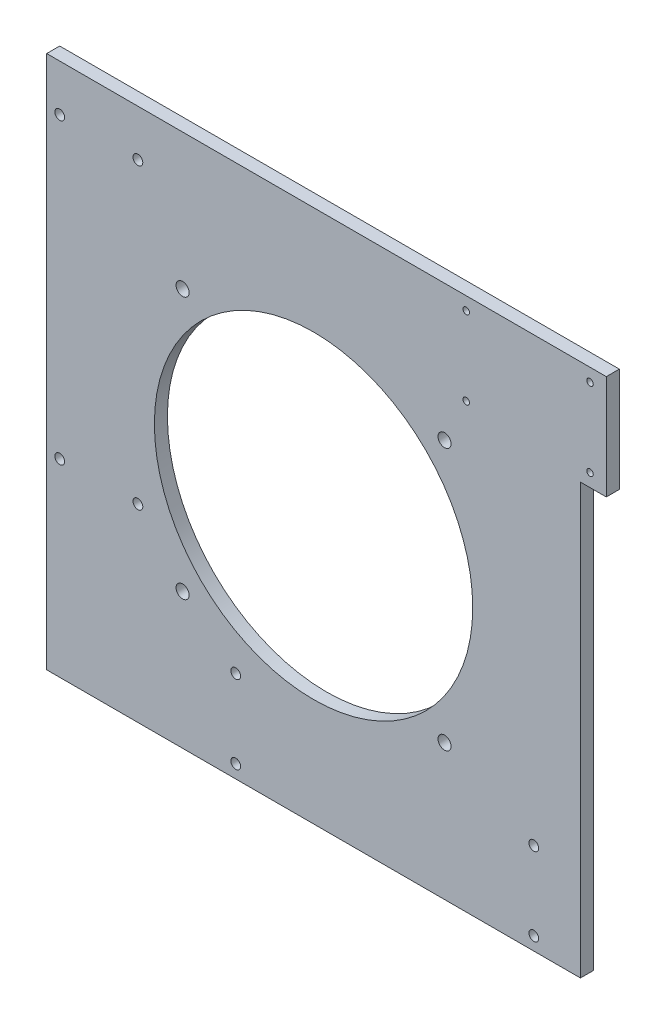
SolidWorks part; units mm, degrees
material "Perspex (TM) GS Acrylic Cast Sheet"
ref_plane "Front Plane" through (0, 0, 0) normal (0, 0, 1) x (1, 0, 0)
ref_plane "Top Plane" through (0, 0, 0) normal (0, 1, 0) x (1, 0, 0)
ref_plane "Right Plane" through (0, 0, 0) normal (1, 0, 0) x (0, 0, -1)
sketch "Sketch1" plane through (0, 0, 0) normal (0, 0, 1) x (1, 0, 0)
  line L1 (0, 0) -> (260.096, 0)
  line L2 (0, 0) -> (0, 260.096)
  line L3 (0, 260.096) -> (260.096, 260.096)
  line L4 (260.096, 0) -> (260.096, 260.096)
  dimension "D1" = 260.096
  dimension "D2" = 260.096
extrude "Boss-Extrude1" add sketch "Sketch1" along normal blind 6.35 contours L3 L4 L1 L2
sketch "Sketch2" plane through (0, 0, 6.35) normal (0, 0, 1) x (1, 0, 0)
  line L0 (-199872.7568, 50.896) -> (200270.8201, 50.896) construction
  line L1 (-199872.7568, 50.896) -> (200270.8201, 50.896) construction
  line L2 (130.048, 0) -> (130.048, 260.096) construction
  line L3 (0, 0) -> (260.096, 0) construction
  line L4 (0, 260.096) -> (260.096, 260.096) construction
  line L5 (260.096, 130.048) -> (0, 130.048) construction
  line L6 (0, 0) -> (0, 260.096) construction
  line L7 (260.096, 0) -> (260.096, 260.096) construction
  circle A0 centre (130.048, 130.048) radius 79.152 construction
  circle A1 centre (130.048, 130.048) radius 77.5645
  dimension "D1" = 1.5875
extrude "Cut-Extrude1" cut sketch "Sketch2" against normal through all
sketch "Sketch3" plane through (0, 0, 0) normal (0, 0, -1) x (-1, 0, 0)
  line L0 (-272.7, 209.296) -> (-272.7, 260.096) construction
  line L1 (-272.7, 209.296) -> (-272.7, 260.096)
  line L2 (-272.7, 209.296) -> (-260.096, 209.296)
  line L3 (-260.096, 0) -> (-260.096, 260.096) construction
  line L4 (-260.096, 209.296) -> (-260.096, 260.096)
  line L5 (-260.096, 260.096) -> (-272.7, 260.096)
extrude "Boss-Extrude2" add sketch "Sketch3" against normal up to surface (6.35 mm away) up to face at (207.6125, 130.048, 6.35)
sketch "Sketch5" plane through (0, 0, 6.35) normal (0, 0, 1) x (1, 0, 0)
  line L0 (260.096, 0) -> (0, 260.096) construction
  line L1 (260.096, 260.096) -> (0, 0) construction
  line L2 (0, 260.096) -> (272.7, 260.096) construction
  line L3 (260.096, 209.296) -> (260.096, 260.096) construction
  line L6 (0, 130.048) -> (260.096, 130.048) construction
  line L9 (0, 0) -> (0, 260.096) construction
  line L10 (260.096, 0) -> (260.096, 209.296) construction
  line L11 (0, 0) -> (260.096, 0) construction
  circle A0 centre (193.8746, 66.2214) radius 3.175
  circle A1 centre (130.048, 130.048) radius 77.5645 construction
  circle A2 centre (66.2214, 193.8746) radius 3.175
  circle A3 centre (193.8746, 193.8746) radius 3.175
  circle A4 centre (66.2214, 66.2214) radius 3.175
  point P3 (184.8944, 75.2016)
  dimension "D2" = 6.35
  dimension "D1" = 12.7
extrude "Cut-Extrude2" cut sketch "Sketch5" against normal through all
sketch "Sketch6" plane through (0, 0, 6.35) normal (0, 0, 1) x (1, 0, 0)
  circle A0 centre (264.7625, 253.746) radius 1.5875 construction
  circle A1 centre (264.7625, 215.646) radius 1.5875 construction
  circle A2 centre (204.4375, 253.746) radius 1.5875 construction
  circle A3 centre (204.4375, 215.646) radius 1.5875 construction
  circle A4 centre (264.7625, 253.746) radius 1.5875
  circle A5 centre (264.7625, 215.646) radius 1.5875
  circle A6 centre (204.4375, 253.746) radius 1.5875
  circle A7 centre (204.4375, 215.646) radius 1.5875
extrude "Cut-Extrude3" cut sketch "Sketch6" against normal through all
sketch "Sketch7" plane through (0, 0, 6.35) normal (0, 0, 1) x (1, 0, 0)
  circle A0 centre (44.45, 237.4741) radius 2.3813 construction
  circle A1 centre (6.35, 237.4741) radius 2.3813 construction
  circle A2 centre (6.35, 92.2179) radius 2.3812 construction
  circle A3 centre (44.45, 92.2179) radius 2.3813 construction
  circle A4 centre (44.45, 237.4741) radius 2.3812
  circle A5 centre (6.35, 237.4741) radius 2.3813
  circle A6 centre (6.35, 92.2179) radius 2.3812
  circle A7 centre (44.45, 92.2179) radius 2.3812
  circle A8 centre (92.1219, 6.446) radius 2.3812 construction
  circle A9 centre (92.1219, 44.546) radius 2.3813 construction
  circle A10 centre (237.3781, 6.446) radius 2.3813 construction
  circle A11 centre (237.3781, 44.546) radius 2.3813 construction
  circle A12 centre (92.1219, 6.446) radius 2.3812
  circle A13 centre (92.1219, 44.546) radius 2.3813
  circle A14 centre (237.3781, 6.446) radius 2.3813
  circle A15 centre (237.3781, 44.546) radius 2.3813
extrude "Cut-Extrude4" cut sketch "Sketch7" against normal through all
